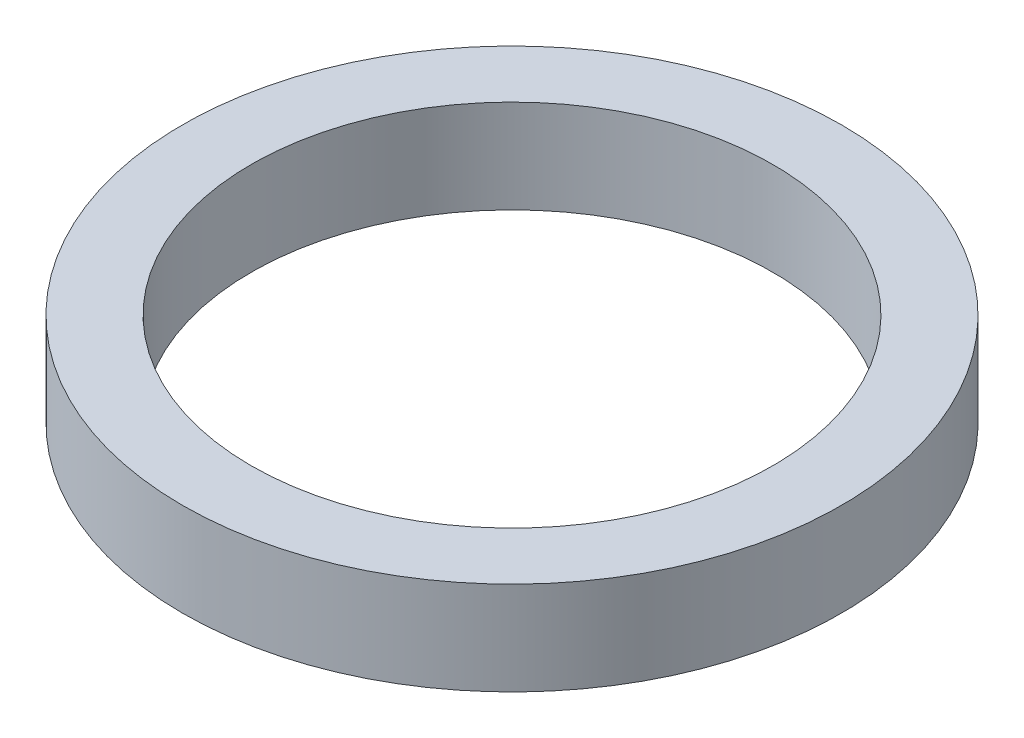
SolidWorks part; units mm, degrees
ref_plane "Front Plane" through (0, 0, 0) normal (0, 0, 1) x (1, 0, 0)
ref_plane "Top Plane" through (0, 0, 0) normal (0, 1, 0) x (1, 0, 0)
ref_plane "Right Plane" through (0, 0, 0) normal (1, 0, 0) x (0, 0, -1)
sketch "Sketch1" plane through (0, 0, 0) normal (0, 1, 0) x (1, 0, 0)
  circle A0 centre (0, 0) radius 60
  dimension "FLANGE_OD" = 120
extrude "Boss-Extrude1" add sketch "Sketch1" along normal blind 17
sketch "Sketch2" plane through (0, 0, 0) normal (0, 1, 0) x (1, 0, 0)
  circle A0 centre (0, 0) radius 47.5
  dimension "BORE_D" = 95
extrude "Cut-Extrude1" cut sketch "Sketch2" along normal through all
sketch "Sketch3" plane through (0, 17, 0) normal (0, 1, 0) x (1, 0, 0)
  circle A0 centre (0, 0) radius 25.8593 construction
  circle A1 centre (-25.8593, 0) radius 1.7659
  dimension "BOLT_D" = 3.5317
  dimension "BOLT_PCD" = 51.7187
extrude "Cut-Extrude2" cut sketch "Sketch3" against normal blind 16.6351 rebuild error yes
pattern_circular "CirPattern1" count 3 over 360 rebuild error yes
